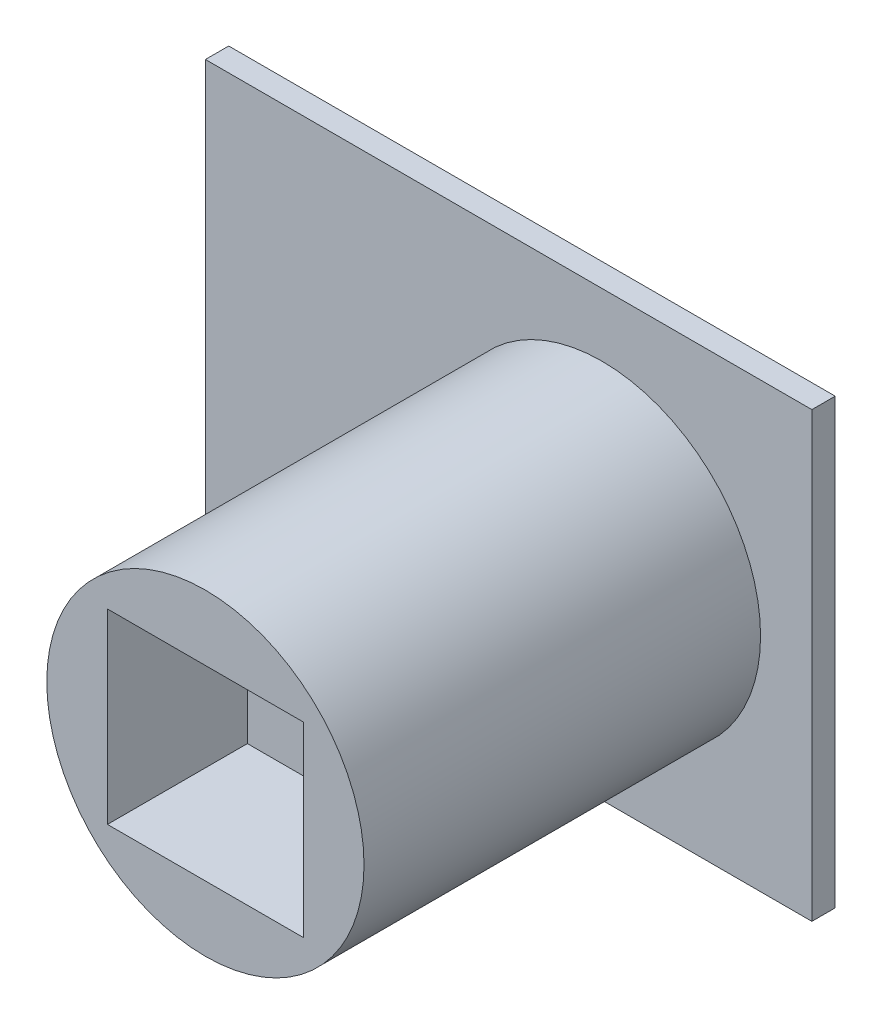
SolidWorks part; units mm, degrees
ref_plane "Alzado" through (0, 0, 0) normal (0, 0, 1) x (1, 0, 0)
ref_plane "Planta" through (0, 0, 0) normal (0, 1, 0) x (1, 0, 0)
ref_plane "Vista lateral" through (0, 0, 0) normal (1, 0, 0) x (0, 0, -1)
sketch "Croquis1" plane through (0, 0, 0) normal (0, 0, 1) x (1, 0, 0)
  line L1 (-65, -47.5) -> (65, -47.5)
  line L2 (-65, -47.5) -> (-65, 47.5)
  line L3 (-65, 47.5) -> (65, 47.5)
  line L4 (65, -47.5) -> (65, 47.5)
  line L5 (-65, -47.5) -> (65, 47.5) construction
  line L6 (-65, 47.5) -> (65, -47.5) construction
  point P0 (0, 0)
  dimension "D1" = 130
  dimension "D2" = 95
extrude "Saliente-Extruir1" add sketch "Croquis1" along normal blind 5
sketch "Croquis2" plane through (0, 0, 5) normal (0, 0, 1) x (1, 0, 0)
  line L0 (0, 0) -> (20, 0) construction
  circle A0 centre (20, 0) radius 34
  dimension "D2" = 68
  dimension "D1" = 20
extrude "Saliente-Extruir2" add sketch "Croquis2" along normal blind 85
sketch "Croquis3" plane through (0, 0, 90) normal (0, 0, 1) x (1, 0, 0)
  line L1 (-1, -20) -> (41, -20)
  line L2 (-1, -20) -> (-1, 20)
  line L3 (-1, 20) -> (41, 20)
  line L4 (41, -20) -> (41, 20)
  line L5 (-1, -20) -> (41, 20) construction
  line L6 (-1, 20) -> (41, -20) construction
  point P0 (20, 0)
  dimension "D1" = 42
  dimension "D2" = 40
extrude "Cortar-Extruir1" cut sketch "Croquis3" against normal blind 30
ref_plane "Plano1" through (0, 0, 0) normal (0, -1, 0) x (-1, 0, 0)
ref_axis "Eje1" through (20, 0, 90) along (0, 0, -1)
